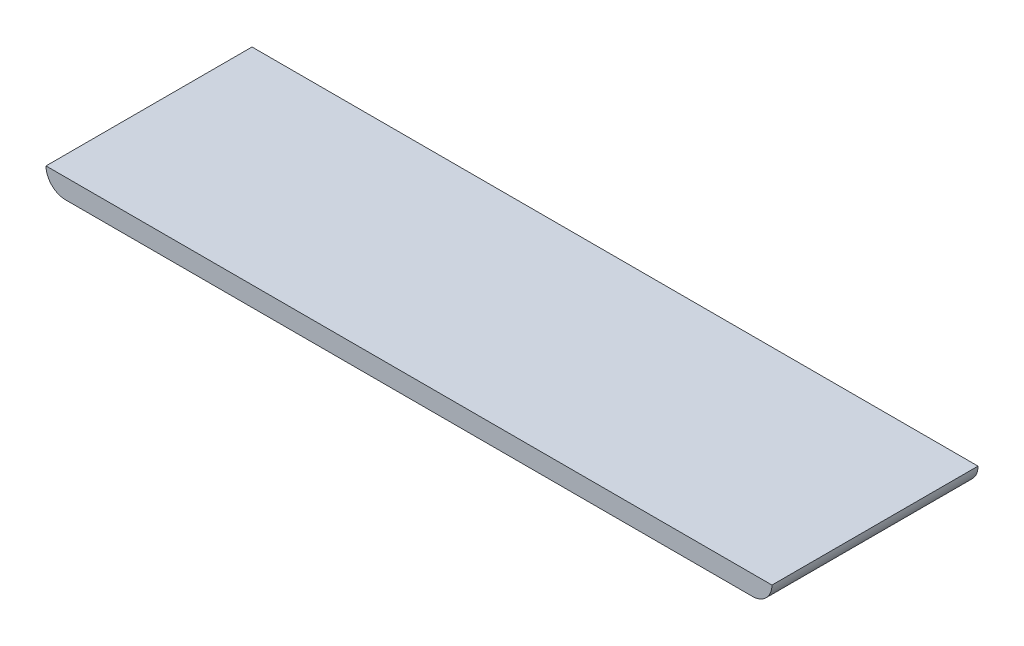
SolidWorks part; units mm, degrees
ref_plane "Спереди" through (0, 0, 0) normal (0, 0, 1) x (1, 0, 0)
ref_plane "Сверху" through (0, 0, 0) normal (0, 1, 0) x (1, 0, 0)
ref_plane "Справа" through (0, 0, 0) normal (1, 0, 0) x (0, 0, -1)
other "Configuration Table"
sketch "Эскиз1" plane through (0, 0, 0) normal (0, 1, 0) x (1, 0, 0)
  line L1 (-2, -31.5) -> (109, -31.5)
  line L2 (-2, -31.5) -> (-2, 0)
  line L3 (-2, 0) -> (109, 0)
  line L4 (109, -31.5) -> (109, 0)
extrude "Бобышка-Вытянуть1" add sketch "Эскиз1" along normal blind 3
fillet "tool_D3_R3_front_outer_corners" radius 3 2 edges at (-2, 0, 15.75) (109, 0, 15.75)
